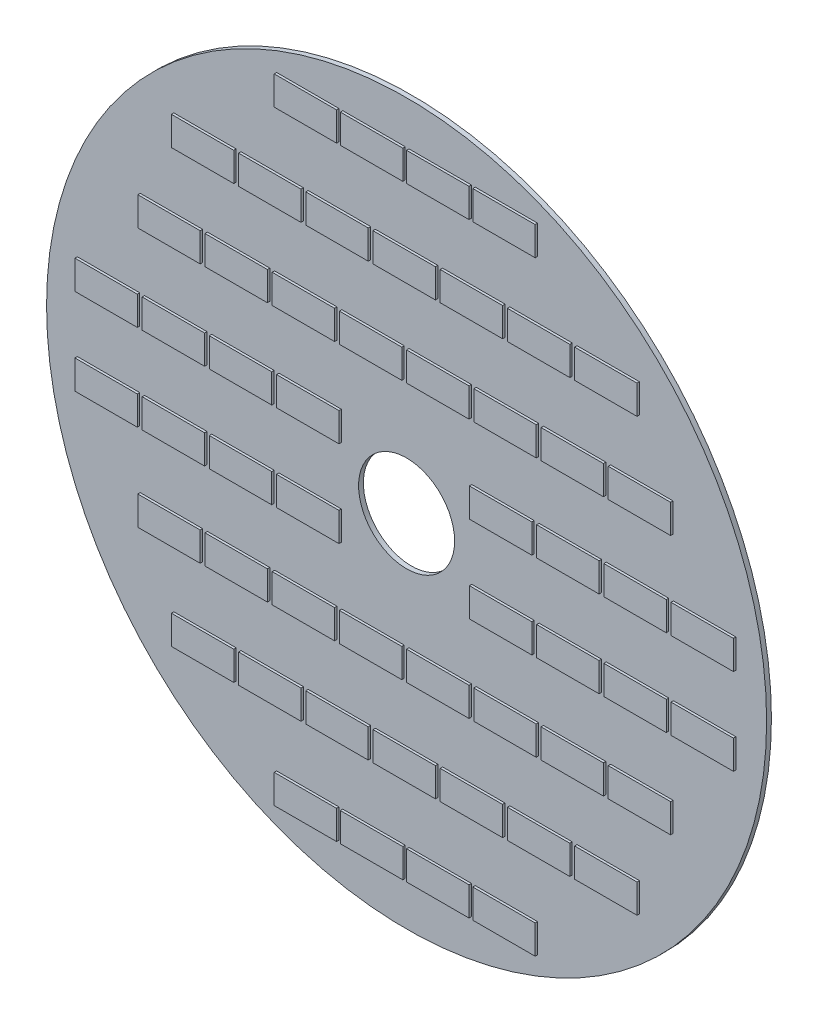
SolidWorks part; units mm, degrees
ref_plane "前视基准面" through (0, 0, 0) normal (0, 0, 1) x (1, 0, 0)
ref_plane "上视基准面" through (0, 0, 0) normal (0, 1, 0) x (1, 0, 0)
ref_plane "右视基准面" through (0, 0, 0) normal (1, 0, 0) x (0, 0, -1)
other "Configuration Table"
sketch "草图1" plane through (0, 0, 0) normal (0, 0, 1) x (1, 0, 0)
  line L5 (100, 90) -> (230, 90)
  line L6 (100, 90) -> (100, 30)
  line L8 (100, 30) -> (230, 30)
  line L12 (230, 90) -> (230, 30)
  line L14 (100, 90) -> (230, 30) construction
  line L18 (100, 30) -> (230, 90) construction
  line L24 (-1658.199, 0) -> (1658.199, 0) construction
  line L26 (0, 1113.9389) -> (0, -1113.9389) construction
  line L50 (300, 90) -> (430, 90)
  line L53 (300, 90) -> (300, 30)
  line L57 (300, 30) -> (430, 30)
  line L58 (430, 90) -> (430, 30)
  line L59 (300, 90) -> (430, 30) construction
  line L60 (300, 30) -> (430, 90) construction
  line L61 (37.3566, 180) -> (37.3566, 120)
  line L62 (237.3566, 120) -> (367.3566, 120)
  line L63 (237.3566, 180) -> (367.3566, 120) construction
  line L64 (37.3566, 120) -> (167.3566, 180) construction
  line L65 (237.3566, 180) -> (237.3566, 120)
  line L66 (367.3566, 180) -> (367.3566, 120)
  line L67 (37.3566, 180) -> (167.3566, 180)
  line L68 (37.3566, 180) -> (167.3566, 120) construction
  line L69 (237.3566, 180) -> (367.3566, 180)
  line L70 (237.3566, 120) -> (367.3566, 180) construction
  line L71 (37.3566, 120) -> (167.3566, 120)
  line L72 (167.3566, 180) -> (167.3566, 120)
  line L83 (37.3566, 364.2375) -> (37.3566, 304.2375)
  line L84 (237.3566, 304.2375) -> (367.3566, 304.2375)
  line L91 (133.7252, 270) -> (133.7252, 210)
  line L92 (333.7252, 210) -> (463.7252, 210)
  line L93 (333.7252, 270) -> (463.7252, 210) construction
  line L94 (133.7252, 210) -> (266.6142, 270) construction
  line L95 (333.7252, 270) -> (333.7252, 210)
  line L96 (463.7252, 270) -> (463.7252, 210)
  line L97 (133.7252, 270) -> (266.6142, 270)
  line L98 (133.7252, 270) -> (266.6142, 210) construction
  line L99 (333.7252, 270) -> (463.7252, 270)
  line L100 (333.7252, 210) -> (463.7252, 270) construction
  line L101 (133.7252, 210) -> (266.6142, 210)
  line L102 (266.6142, 270) -> (266.6142, 210)
  line L103 (-65, 274.2375) -> (-65, 210)
  line L104 (-65, 274.2375) -> (65, 274.2375)
  line L105 (-65, 210) -> (65, 210)
  line L106 (65, 274.2375) -> (65, 210)
  line L107 (-65, 210) -> (65, 274.2375) construction
  line L108 (-65, 274.2375) -> (65, 210) construction
  line L109 (-264.8303, 270) -> (-264.8303, 210)
  line L110 (-264.8303, 270) -> (-134.8303, 270)
  line L111 (-264.8303, 210) -> (-134.8303, 210)
  line L112 (-134.8303, 270) -> (-134.8303, 210)
  line L113 (-264.8303, 210) -> (-134.8303, 270) construction
  line L114 (-264.8303, 270) -> (-134.8303, 210) construction
  line L115 (-464.8303, 270) -> (-464.8303, 210)
  line L116 (-464.8303, 270) -> (-334.8303, 270)
  line L117 (-464.8303, 210) -> (-334.8303, 210)
  line L118 (-334.8303, 270) -> (-334.8303, 210)
  line L119 (-464.8303, 210) -> (-334.8303, 270) construction
  line L120 (-464.8303, 270) -> (-334.8303, 210) construction
  line L122 (237.3566, 364.2375) -> (237.3566, 304.2375)
  line L123 (367.3566, 364.2375) -> (367.3566, 304.2375)
  line L125 (37.3566, 364.2375) -> (167.3566, 364.2375)
  line L127 (237.3566, 364.2375) -> (367.3566, 364.2375)
  line L128 (37.3566, 304.2375) -> (167.3566, 304.2375)
  line L129 (167.3566, 364.2375) -> (167.3566, 304.2375)
  line L139 (237.3566, 364.2375) -> (367.3566, 304.2375) construction
  line L140 (37.3566, 304.2375) -> (167.3566, 364.2375) construction
  line L141 (37.3566, 364.2375) -> (167.3566, 304.2375) construction
  line L142 (237.3566, 304.2375) -> (367.3566, 364.2375) construction
  line L143 (37.3566, 450) -> (37.3566, 390)
  line L144 (237.3566, 390) -> (367.3566, 390)
  line L145 (237.3566, 450) -> (237.3566, 390)
  line L146 (367.3566, 450) -> (367.3566, 390)
  line L147 (37.3566, 450) -> (167.3566, 450)
  line L148 (237.3566, 450) -> (367.3566, 450)
  line L149 (37.3566, 390) -> (167.3566, 390)
  line L150 (167.3566, 450) -> (167.3566, 390)
  line L151 (237.3566, 450) -> (367.3566, 390) construction
  line L152 (37.3566, 390) -> (167.3566, 450) construction
  line L153 (37.3566, 450) -> (167.3566, 390) construction
  line L154 (237.3566, 390) -> (367.3566, 450) construction
  line L155 (37.3566, 535.7625) -> (37.3566, 475.7625)
  line L156 (237.3566, 475.7625) -> (367.3566, 475.7625)
  line L157 (237.3566, 535.7625) -> (237.3566, 475.7625)
  line L158 (367.3566, 535.7625) -> (367.3566, 475.7625)
  line L159 (37.3566, 535.7625) -> (167.3566, 535.7625)
  line L160 (237.3566, 535.7625) -> (367.3566, 535.7625)
  line L161 (37.3566, 475.7625) -> (167.3566, 475.7625)
  line L162 (167.3566, 535.7625) -> (167.3566, 475.7625)
  line L163 (237.3566, 535.7625) -> (367.3566, 475.7625) construction
  line L164 (37.3566, 475.7625) -> (167.3566, 535.7625) construction
  line L165 (37.3566, 535.7625) -> (167.3566, 475.7625) construction
  line L166 (237.3566, 475.7625) -> (367.3566, 535.7625) construction
  line L167 (-264.8303, 565.7625) -> (-134.8303, 625.7625) construction
  line L168 (133.7252, 565.7625) -> (266.6142, 565.7625)
  line L169 (-65, 565.7625) -> (65, 625.7625) construction
  line L170 (-65, 625.7625) -> (-65, 565.7625)
  line L171 (-264.8303, 625.7625) -> (-264.8303, 565.7625)
  line L172 (-134.8303, 625.7625) -> (-134.8303, 565.7625)
  line L173 (133.7252, 625.7625) -> (266.6142, 625.7625)
  line L174 (133.7252, 625.7625) -> (266.6142, 565.7625) construction
  line L175 (65, 625.7625) -> (65, 565.7625)
  line L176 (-264.8303, 625.7625) -> (-134.8303, 565.7625) construction
  line L177 (133.7252, 625.7625) -> (133.7252, 565.7625)
  line L178 (-65, 625.7625) -> (65, 625.7625)
  line L179 (-65, 565.7625) -> (65, 565.7625)
  line L180 (-264.8303, 565.7625) -> (-134.8303, 565.7625)
  line L181 (133.7252, 565.7625) -> (266.6142, 625.7625) construction
  line L182 (266.6142, 625.7625) -> (266.6142, 565.7625)
  line L183 (-264.8303, 625.7625) -> (-134.8303, 625.7625)
  line L184 (-65, 625.7625) -> (65, 565.7625) construction
  line L185 (-300, 90) -> (-300, 30)
  line L186 (-300, 30) -> (-430, 30)
  line L187 (-430, 90) -> (-430, 30)
  line L188 (-300, 90) -> (-430, 90)
  line L189 (-100, 30) -> (-230, 30)
  line L190 (-230, 90) -> (-230, 30)
  line L191 (-100, 90) -> (-230, 90)
  line L192 (-100, 90) -> (-100, 30)
  line L193 (-37.3566, 180) -> (-167.3566, 180)
  line L194 (-167.3566, 180) -> (-167.3566, 120)
  line L195 (-37.3566, 120) -> (-167.3566, 120)
  line L196 (-37.3566, 180) -> (-37.3566, 120)
  line L197 (-237.3566, 180) -> (-237.3566, 120)
  line L198 (-237.3566, 180) -> (-367.3566, 180)
  line L199 (-367.3566, 180) -> (-367.3566, 120)
  line L200 (-237.3566, 120) -> (-367.3566, 120)
  line L201 (-237.3566, 475.7625) -> (-367.3566, 535.7625) construction
  line L202 (-37.3566, 535.7625) -> (-167.3566, 475.7625) construction
  line L203 (-37.3566, 475.7625) -> (-167.3566, 535.7625) construction
  line L204 (-237.3566, 535.7625) -> (-367.3566, 475.7625) construction
  line L205 (-237.3566, 390) -> (-367.3566, 450) construction
  line L206 (-37.3566, 450) -> (-167.3566, 390) construction
  line L207 (-37.3566, 390) -> (-167.3566, 450) construction
  line L208 (-237.3566, 450) -> (-367.3566, 390) construction
  line L209 (-237.3566, 304.2375) -> (-367.3566, 364.2375) construction
  line L210 (-37.3566, 364.2375) -> (-167.3566, 304.2375) construction
  line L211 (-37.3566, 304.2375) -> (-167.3566, 364.2375) construction
  line L212 (-237.3566, 364.2375) -> (-367.3566, 304.2375) construction
  line L213 (-167.3566, 535.7625) -> (-167.3566, 475.7625)
  line L214 (-37.3566, 475.7625) -> (-167.3566, 475.7625)
  line L215 (-237.3566, 535.7625) -> (-367.3566, 535.7625)
  line L216 (-37.3566, 535.7625) -> (-167.3566, 535.7625)
  line L217 (-367.3566, 535.7625) -> (-367.3566, 475.7625)
  line L218 (-237.3566, 535.7625) -> (-237.3566, 475.7625)
  line L219 (-237.3566, 475.7625) -> (-367.3566, 475.7625)
  line L220 (-37.3566, 535.7625) -> (-37.3566, 475.7625)
  line L221 (-167.3566, 450) -> (-167.3566, 390)
  line L222 (-37.3566, 390) -> (-167.3566, 390)
  line L223 (-237.3566, 450) -> (-367.3566, 450)
  line L224 (-37.3566, 450) -> (-167.3566, 450)
  line L225 (-367.3566, 450) -> (-367.3566, 390)
  line L226 (-237.3566, 450) -> (-237.3566, 390)
  line L227 (-237.3566, 390) -> (-367.3566, 390)
  line L228 (-37.3566, 450) -> (-37.3566, 390)
  line L229 (-167.3566, 364.2375) -> (-167.3566, 304.2375)
  line L230 (-37.3566, 304.2375) -> (-167.3566, 304.2375)
  line L231 (-237.3566, 364.2375) -> (-367.3566, 364.2375)
  line L232 (-37.3566, 364.2375) -> (-167.3566, 364.2375)
  line L233 (-367.3566, 364.2375) -> (-367.3566, 304.2375)
  line L234 (-237.3566, 364.2375) -> (-237.3566, 304.2375)
  line L235 (-237.3566, 304.2375) -> (-367.3566, 304.2375)
  line L236 (-37.3566, 364.2375) -> (-37.3566, 304.2375)
  line L237 (-237.3566, -364.2375) -> (-367.3566, -304.2375) construction
  line L238 (-37.3566, -304.2375) -> (-167.3566, -364.2375) construction
  line L239 (-37.3566, -364.2375) -> (-167.3566, -304.2375) construction
  line L240 (-237.3566, -304.2375) -> (-367.3566, -364.2375) construction
  line L241 (-237.3566, -450) -> (-367.3566, -390) construction
  line L242 (-37.3566, -390) -> (-167.3566, -450) construction
  line L243 (-37.3566, -450) -> (-167.3566, -390) construction
  line L244 (-237.3566, -390) -> (-367.3566, -450) construction
  line L245 (-237.3566, -535.7625) -> (-367.3566, -475.7625) construction
  line L246 (-37.3566, -475.7625) -> (-167.3566, -535.7625) construction
  line L247 (-37.3566, -535.7625) -> (-167.3566, -475.7625) construction
  line L248 (-237.3566, -475.7625) -> (-367.3566, -535.7625) construction
  line L249 (-65, -625.7625) -> (65, -565.7625) construction
  line L250 (133.7252, -565.7625) -> (266.6142, -625.7625) construction
  line L251 (-264.8303, -625.7625) -> (-134.8303, -565.7625) construction
  line L252 (133.7252, -625.7625) -> (266.6142, -565.7625) construction
  line L253 (-65, -565.7625) -> (65, -625.7625) construction
  line L254 (-264.8303, -565.7625) -> (-134.8303, -625.7625) construction
  line L255 (237.3566, -475.7625) -> (367.3566, -535.7625) construction
  line L256 (37.3566, -535.7625) -> (167.3566, -475.7625) construction
  line L257 (37.3566, -475.7625) -> (167.3566, -535.7625) construction
  line L258 (237.3566, -535.7625) -> (367.3566, -475.7625) construction
  line L259 (237.3566, -390) -> (367.3566, -450) construction
  line L260 (37.3566, -450) -> (167.3566, -390) construction
  line L261 (37.3566, -390) -> (167.3566, -450) construction
  line L262 (237.3566, -450) -> (367.3566, -390) construction
  line L263 (237.3566, -304.2375) -> (367.3566, -364.2375) construction
  line L264 (37.3566, -364.2375) -> (167.3566, -304.2375) construction
  line L265 (37.3566, -304.2375) -> (167.3566, -364.2375) construction
  line L266 (237.3566, -364.2375) -> (367.3566, -304.2375) construction
  line L267 (-464.8303, -270) -> (-334.8303, -210) construction
  line L268 (-464.8303, -210) -> (-334.8303, -270) construction
  line L269 (-264.8303, -270) -> (-134.8303, -210) construction
  line L270 (-264.8303, -210) -> (-134.8303, -270) construction
  line L271 (-65, -274.2375) -> (65, -210) construction
  line L272 (-65, -210) -> (65, -274.2375) construction
  line L273 (333.7252, -210) -> (463.7252, -270) construction
  line L274 (133.7252, -270) -> (266.6142, -210) construction
  line L275 (133.7252, -210) -> (266.6142, -270) construction
  line L276 (333.7252, -270) -> (463.7252, -210) construction
  line L277 (237.3566, -120) -> (367.3566, -180) construction
  line L278 (37.3566, -180) -> (167.3566, -120) construction
  line L279 (37.3566, -120) -> (167.3566, -180) construction
  line L280 (237.3566, -180) -> (367.3566, -120) construction
  line L281 (300, -30) -> (430, -90) construction
  line L282 (300, -90) -> (430, -30) construction
  line L283 (100, -30) -> (230, -90) construction
  line L284 (100, -90) -> (230, -30) construction
  line L285 (-37.3566, -364.2375) -> (-37.3566, -304.2375)
  line L286 (-237.3566, -304.2375) -> (-367.3566, -304.2375)
  line L287 (-237.3566, -364.2375) -> (-237.3566, -304.2375)
  line L288 (-367.3566, -364.2375) -> (-367.3566, -304.2375)
  line L289 (-37.3566, -364.2375) -> (-167.3566, -364.2375)
  line L290 (-237.3566, -364.2375) -> (-367.3566, -364.2375)
  line L291 (-37.3566, -304.2375) -> (-167.3566, -304.2375)
  line L292 (-167.3566, -364.2375) -> (-167.3566, -304.2375)
  line L293 (-37.3566, -450) -> (-37.3566, -390)
  line L294 (-237.3566, -390) -> (-367.3566, -390)
  line L295 (-237.3566, -450) -> (-237.3566, -390)
  line L296 (-367.3566, -450) -> (-367.3566, -390)
  line L297 (-37.3566, -450) -> (-167.3566, -450)
  line L298 (-237.3566, -450) -> (-367.3566, -450)
  line L299 (-37.3566, -390) -> (-167.3566, -390)
  line L300 (-167.3566, -450) -> (-167.3566, -390)
  line L301 (-37.3566, -535.7625) -> (-37.3566, -475.7625)
  line L302 (-237.3566, -475.7625) -> (-367.3566, -475.7625)
  line L303 (-237.3566, -535.7625) -> (-237.3566, -475.7625)
  line L304 (-367.3566, -535.7625) -> (-367.3566, -475.7625)
  line L305 (-37.3566, -535.7625) -> (-167.3566, -535.7625)
  line L306 (-237.3566, -535.7625) -> (-367.3566, -535.7625)
  line L307 (-37.3566, -475.7625) -> (-167.3566, -475.7625)
  line L308 (-167.3566, -535.7625) -> (-167.3566, -475.7625)
  line L309 (-237.3566, -120) -> (-367.3566, -120)
  line L310 (-367.3566, -180) -> (-367.3566, -120)
  line L311 (-237.3566, -180) -> (-367.3566, -180)
  line L312 (-237.3566, -180) -> (-237.3566, -120)
  line L313 (-37.3566, -180) -> (-37.3566, -120)
  line L314 (-37.3566, -120) -> (-167.3566, -120)
  line L315 (-167.3566, -180) -> (-167.3566, -120)
  line L316 (-37.3566, -180) -> (-167.3566, -180)
  line L317 (-100, -90) -> (-100, -30)
  line L318 (-100, -90) -> (-230, -90)
  line L319 (-230, -90) -> (-230, -30)
  line L320 (-100, -30) -> (-230, -30)
  line L321 (-300, -90) -> (-430, -90)
  line L322 (-430, -90) -> (-430, -30)
  line L323 (-300, -30) -> (-430, -30)
  line L324 (-300, -90) -> (-300, -30)
  line L325 (-264.8303, -625.7625) -> (-134.8303, -625.7625)
  line L326 (266.6142, -625.7625) -> (266.6142, -565.7625)
  line L327 (-264.8303, -565.7625) -> (-134.8303, -565.7625)
  line L328 (-65, -565.7625) -> (65, -565.7625)
  line L329 (-65, -625.7625) -> (65, -625.7625)
  line L330 (133.7252, -625.7625) -> (133.7252, -565.7625)
  line L331 (65, -625.7625) -> (65, -565.7625)
  line L332 (133.7252, -625.7625) -> (266.6142, -625.7625)
  line L333 (-134.8303, -625.7625) -> (-134.8303, -565.7625)
  line L334 (-264.8303, -625.7625) -> (-264.8303, -565.7625)
  line L335 (-65, -625.7625) -> (-65, -565.7625)
  line L336 (133.7252, -565.7625) -> (266.6142, -565.7625)
  line L337 (167.3566, -535.7625) -> (167.3566, -475.7625)
  line L338 (37.3566, -475.7625) -> (167.3566, -475.7625)
  line L339 (237.3566, -535.7625) -> (367.3566, -535.7625)
  line L340 (37.3566, -535.7625) -> (167.3566, -535.7625)
  line L341 (367.3566, -535.7625) -> (367.3566, -475.7625)
  line L342 (237.3566, -535.7625) -> (237.3566, -475.7625)
  line L343 (237.3566, -475.7625) -> (367.3566, -475.7625)
  line L344 (37.3566, -535.7625) -> (37.3566, -475.7625)
  line L345 (167.3566, -450) -> (167.3566, -390)
  line L346 (37.3566, -390) -> (167.3566, -390)
  line L347 (237.3566, -450) -> (367.3566, -450)
  line L348 (37.3566, -450) -> (167.3566, -450)
  line L349 (367.3566, -450) -> (367.3566, -390)
  line L350 (237.3566, -450) -> (237.3566, -390)
  line L351 (237.3566, -390) -> (367.3566, -390)
  line L352 (37.3566, -450) -> (37.3566, -390)
  line L353 (167.3566, -364.2375) -> (167.3566, -304.2375)
  line L354 (37.3566, -304.2375) -> (167.3566, -304.2375)
  line L355 (237.3566, -364.2375) -> (367.3566, -364.2375)
  line L356 (37.3566, -364.2375) -> (167.3566, -364.2375)
  line L357 (367.3566, -364.2375) -> (367.3566, -304.2375)
  line L358 (237.3566, -364.2375) -> (237.3566, -304.2375)
  line L359 (-334.8303, -270) -> (-334.8303, -210)
  line L360 (-464.8303, -210) -> (-334.8303, -210)
  line L361 (-464.8303, -270) -> (-334.8303, -270)
  line L362 (-464.8303, -270) -> (-464.8303, -210)
  line L363 (-134.8303, -270) -> (-134.8303, -210)
  line L364 (-264.8303, -210) -> (-134.8303, -210)
  line L365 (-264.8303, -270) -> (-134.8303, -270)
  line L366 (-264.8303, -270) -> (-264.8303, -210)
  line L367 (65, -274.2375) -> (65, -210)
  line L368 (-65, -210) -> (65, -210)
  line L369 (-65, -274.2375) -> (65, -274.2375)
  line L370 (-65, -274.2375) -> (-65, -210)
  line L371 (266.6142, -270) -> (266.6142, -210)
  line L372 (133.7252, -210) -> (266.6142, -210)
  line L373 (333.7252, -270) -> (463.7252, -270)
  line L374 (133.7252, -270) -> (266.6142, -270)
  line L375 (463.7252, -270) -> (463.7252, -210)
  line L376 (333.7252, -270) -> (333.7252, -210)
  line L377 (333.7252, -210) -> (463.7252, -210)
  line L378 (133.7252, -270) -> (133.7252, -210)
  line L379 (237.3566, -304.2375) -> (367.3566, -304.2375)
  line L380 (37.3566, -364.2375) -> (37.3566, -304.2375)
  line L381 (167.3566, -180) -> (167.3566, -120)
  line L382 (37.3566, -120) -> (167.3566, -120)
  line L383 (237.3566, -180) -> (367.3566, -180)
  line L384 (37.3566, -180) -> (167.3566, -180)
  line L385 (367.3566, -180) -> (367.3566, -120)
  line L386 (237.3566, -180) -> (237.3566, -120)
  line L387 (237.3566, -120) -> (367.3566, -120)
  line L388 (37.3566, -180) -> (37.3566, -120)
  line L389 (430, -90) -> (430, -30)
  line L390 (300, -30) -> (430, -30)
  line L391 (300, -90) -> (300, -30)
  line L392 (300, -90) -> (430, -90)
  line L393 (230, -90) -> (230, -30)
  line L394 (100, -30) -> (230, -30)
  line L395 (100, -90) -> (100, -30)
  line L396 (100, -90) -> (230, -90)
  line L397 (-65, 715.7625) -> (65, 715.7625)
  line L398 (-65, 715.7625) -> (65, 655.7625) construction
  line L399 (65, 715.7625) -> (65, 655.7625)
  line L400 (-65, 655.7625) -> (65, 715.7625) construction
  line L401 (-65, 715.7625) -> (-65, 655.7625)
  line L402 (-65, 655.7625) -> (65, 655.7625)
  line L403 (-65, -655.7625) -> (65, -715.7625) construction
  line L404 (-65, -715.7625) -> (65, -655.7625) construction
  line L405 (-65, -655.7625) -> (65, -655.7625)
  line L406 (-65, -715.7625) -> (-65, -655.7625)
  line L407 (65, -715.7625) -> (65, -655.7625)
  line L408 (-65, -715.7625) -> (65, -715.7625)
  circle A0 centre (0, 0) radius 750 construction
  point P0 (165, 60)
  point P5 (102.3566, 150)
  point P7 (365, 60)
  point P16 (302.3566, 192.8005)
  point P24 (200.1697, 595.7625)
  point P26 (200.1697, 240)
  point P29 (102.3566, 334.2375)
  point P39 (102.3566, 420)
  point P47 (0, 274.2375)
  point P70 (102.3566, 505.7625)
  point P80 (302.3566, 462.8005)
  point P81 (302.3566, 377.038)
  point P132 (-102.3566, 505.7625)
  point P133 (-102.3566, 420)
  point P134 (-102.3566, 334.2375)
  point P247 (-102.3566, -334.2375)
  point P248 (-102.3566, -420)
  point P249 (-102.3566, -505.7625)
  point P250 (102.3566, -505.7625)
  point P251 (102.3566, -420)
  point P252 (102.3566, -334.2375)
  point P253 (200.1697, -240)
  point P254 (200.1697, -595.7625)
  point P255 (302.3566, -192.8005)
  point P256 (365, -60)
  point P257 (102.3566, -150)
  point P258 (165, -60)
  dimension "D3" = 100
  dimension "D1" = 2
  dimension "D2" = 30
  dimension "D4" = 30
  dimension "D5" = 60
  dimension "D6" = 130
  dimension "D7" = 70
  dimension "D8" = 70
  dimension "D9" = 2
  dimension "D10" = 3
  dimension "D11" = 130
  dimension "D12" = 60
  dimension "D13" = 30
  dimension "D14" = 60
  dimension "D15" = 30
sketch "草图2" plane through (0, 0, 0) normal (0, 0, 1) x (1, 0, 0)
  circle A0 centre (0, 0) radius 750
  circle A1 centre (0, 0) radius 100
  dimension "D1" = 1500
  dimension "D2" = 200
extrude "凸台-拉伸1" add sketch "草图2" along normal blind 10
sketch "草图3" plane through (0, 0, 0) normal (0, 0, 1) x (1, 0, 0)
  line L0 (-1673.2224, 0) -> (1673.2224, 0) construction
  line L2 (135.9057, 120) -> (265.9057, 120)
  line L3 (0, -869.8968) -> (0, 1064.1184) construction
  line L4 (135.9057, 120) -> (135.9057, 60)
  line L5 (135.9057, 60) -> (265.9057, 60)
  line L6 (265.9057, 120) -> (265.9057, 60)
  line L18 (275.9057, 120) -> (275.9057, 60)
  line L19 (275.9057, 120) -> (405.9057, 120)
  line L20 (405.9057, 120) -> (405.9057, 60)
  line L21 (275.9057, 60) -> (405.9057, 60)
  line L22 (415.9057, 120) -> (415.9057, 60)
  line L23 (415.9057, 120) -> (545.9057, 120)
  line L24 (545.9057, 120) -> (545.9057, 60)
  line L25 (415.9057, 60) -> (545.9057, 60)
  line L26 (555.9057, 120) -> (555.9057, 60)
  line L27 (555.9057, 120) -> (685.9057, 120)
  line L28 (685.9057, 120) -> (685.9057, 60)
  line L29 (555.9057, 60) -> (685.9057, 60)
  line L30 (145, 300) -> (145, 240)
  line L31 (-555.9057, 60) -> (-685.9057, 60)
  line L32 (-685.9057, 120) -> (-685.9057, 60)
  line L33 (-555.9057, 120) -> (-685.9057, 120)
  line L34 (-555.9057, 120) -> (-555.9057, 60)
  line L35 (-415.9057, 60) -> (-545.9057, 60)
  line L36 (-545.9057, 120) -> (-545.9057, 60)
  line L37 (-415.9057, 120) -> (-545.9057, 120)
  line L38 (-415.9057, 120) -> (-415.9057, 60)
  line L39 (-275.9057, 60) -> (-405.9057, 60)
  line L40 (-405.9057, 120) -> (-405.9057, 60)
  line L41 (-275.9057, 120) -> (-405.9057, 120)
  line L42 (-275.9057, 120) -> (-275.9057, 60)
  line L43 (-265.9057, 120) -> (-265.9057, 60)
  line L44 (-135.9057, 60) -> (-265.9057, 60)
  line L45 (-135.9057, 120) -> (-135.9057, 60)
  line L46 (-135.9057, 120) -> (-265.9057, 120)
  line L47 (145, 300) -> (275, 300)
  line L48 (5, 300) -> (135, 300)
  line L49 (5, 300) -> (5, 240)
  line L50 (5, 240) -> (135, 240)
  line L51 (135, 300) -> (135, 240)
  line L52 (275, 300) -> (275, 240)
  line L53 (145, 240) -> (275, 240)
  line L54 (285, 300) -> (285, 240)
  line L55 (285, 300) -> (415, 300)
  line L56 (415, 300) -> (415, 240)
  line L57 (285, 240) -> (415, 240)
  line L58 (425, 300) -> (425, 240)
  line L59 (425, 300) -> (555, 300)
  line L60 (555, 300) -> (555, 240)
  line L61 (425, 240) -> (555, 240)
  line L62 (-425, 240) -> (-555, 240)
  line L63 (-555, 300) -> (-555, 240)
  line L64 (-425, 300) -> (-555, 300)
  line L65 (-425, 300) -> (-425, 240)
  line L66 (-285, 240) -> (-415, 240)
  line L67 (-415, 300) -> (-415, 240)
  line L68 (-285, 300) -> (-415, 300)
  line L69 (-285, 300) -> (-285, 240)
  line L70 (-145, 240) -> (-275, 240)
  line L71 (-275, 300) -> (-275, 240)
  line L72 (-135, 300) -> (-135, 240)
  line L73 (-5, 240) -> (-135, 240)
  line L74 (-5, 300) -> (-5, 240)
  line L75 (-5, 300) -> (-135, 300)
  line L76 (-145, 300) -> (-275, 300)
  line L77 (-145, 300) -> (-145, 240)
  line L78 (75, 480) -> (205, 480)
  line L79 (-65, 480) -> (65, 480)
  line L80 (-65, 480) -> (-65, 420)
  line L81 (-65, 420) -> (65, 420)
  line L82 (65, 480) -> (65, 420)
  line L83 (75, 480) -> (75, 420)
  line L84 (75, 420) -> (205, 420)
  line L85 (205, 480) -> (205, 420)
  line L86 (215, 480) -> (345, 480)
  line L87 (215, 480) -> (215, 420)
  line L88 (215, 420) -> (345, 420)
  line L89 (345, 480) -> (345, 420)
  line L90 (355, 480) -> (485, 480)
  line L91 (355, 480) -> (355, 420)
  line L92 (355, 420) -> (485, 420)
  line L93 (485, 480) -> (485, 420)
  line L94 (-485, 480) -> (-485, 420)
  line L95 (-355, 420) -> (-485, 420)
  line L96 (-355, 480) -> (-355, 420)
  line L97 (-355, 480) -> (-485, 480)
  line L98 (-345, 480) -> (-345, 420)
  line L99 (-215, 420) -> (-345, 420)
  line L100 (-215, 480) -> (-215, 420)
  line L101 (-215, 480) -> (-345, 480)
  line L102 (-205, 480) -> (-205, 420)
  line L103 (-75, 420) -> (-205, 420)
  line L104 (-75, 480) -> (-75, 420)
  line L105 (-75, 480) -> (-205, 480)
  line L106 (-132.9073, 660) -> (-132.9073, 600)
  line L107 (-270.8146, 660) -> (-140.8146, 660)
  line L108 (-270.8146, 660) -> (-270.8146, 600)
  line L109 (-270.8146, 600) -> (-140.8146, 600)
  line L110 (-140.8146, 660) -> (-140.8146, 600)
  line L111 (-132.9073, 660) -> (-2.9073, 660)
  line L112 (-2.9073, 660) -> (-2.9073, 600)
  line L113 (-132.9073, 600) -> (-2.9073, 600)
  line L114 (5, 660) -> (5, 600)
  line L115 (5, 660) -> (135, 660)
  line L116 (135, 660) -> (135, 600)
  line L117 (5, 600) -> (135, 600)
  line L118 (142.9073, 660) -> (142.9073, 600)
  line L119 (142.9073, 660) -> (272.9073, 660)
  line L120 (272.9073, 660) -> (272.9073, 600)
  line L121 (142.9073, 600) -> (272.9073, 600)
  line L122 (142.9073, -600) -> (272.9073, -600)
  line L123 (272.9073, -660) -> (272.9073, -600)
  line L124 (142.9073, -660) -> (272.9073, -660)
  line L125 (142.9073, -660) -> (142.9073, -600)
  line L126 (5, -600) -> (135, -600)
  line L127 (135, -660) -> (135, -600)
  line L128 (5, -660) -> (135, -660)
  line L129 (5, -660) -> (5, -600)
  line L130 (-132.9073, -600) -> (-2.9073, -600)
  line L131 (-2.9073, -660) -> (-2.9073, -600)
  line L132 (-132.9073, -660) -> (-2.9073, -660)
  line L133 (-140.8146, -660) -> (-140.8146, -600)
  line L134 (-270.8146, -600) -> (-140.8146, -600)
  line L135 (-270.8146, -660) -> (-270.8146, -600)
  line L136 (-270.8146, -660) -> (-140.8146, -660)
  line L137 (-132.9073, -660) -> (-132.9073, -600)
  line L138 (-75, -480) -> (-205, -480)
  line L139 (-75, -480) -> (-75, -420)
  line L140 (-75, -420) -> (-205, -420)
  line L141 (-205, -480) -> (-205, -420)
  line L142 (-215, -480) -> (-345, -480)
  line L143 (-215, -480) -> (-215, -420)
  line L144 (-215, -420) -> (-345, -420)
  line L145 (-345, -480) -> (-345, -420)
  line L146 (-355, -480) -> (-485, -480)
  line L147 (-355, -480) -> (-355, -420)
  line L148 (-355, -420) -> (-485, -420)
  line L149 (-485, -480) -> (-485, -420)
  line L150 (485, -480) -> (485, -420)
  line L151 (355, -420) -> (485, -420)
  line L152 (355, -480) -> (355, -420)
  line L153 (355, -480) -> (485, -480)
  line L154 (345, -480) -> (345, -420)
  line L155 (215, -420) -> (345, -420)
  line L156 (215, -480) -> (215, -420)
  line L157 (215, -480) -> (345, -480)
  line L158 (205, -480) -> (205, -420)
  line L159 (75, -420) -> (205, -420)
  line L160 (75, -480) -> (75, -420)
  line L161 (65, -480) -> (65, -420)
  line L162 (-65, -420) -> (65, -420)
  line L163 (-65, -480) -> (-65, -420)
  line L164 (-65, -480) -> (65, -480)
  line L165 (75, -480) -> (205, -480)
  line L166 (-145, -300) -> (-145, -240)
  line L167 (-145, -300) -> (-275, -300)
  line L168 (-5, -300) -> (-135, -300)
  line L169 (-5, -300) -> (-5, -240)
  line L170 (-5, -240) -> (-135, -240)
  line L171 (-135, -300) -> (-135, -240)
  line L172 (-275, -300) -> (-275, -240)
  line L173 (-145, -240) -> (-275, -240)
  line L174 (-285, -300) -> (-285, -240)
  line L175 (-285, -300) -> (-415, -300)
  line L176 (-415, -300) -> (-415, -240)
  line L177 (-285, -240) -> (-415, -240)
  line L178 (-425, -300) -> (-425, -240)
  line L179 (-425, -300) -> (-555, -300)
  line L180 (-555, -300) -> (-555, -240)
  line L181 (-425, -240) -> (-555, -240)
  line L182 (425, -240) -> (555, -240)
  line L183 (555, -300) -> (555, -240)
  line L184 (425, -300) -> (555, -300)
  line L185 (425, -300) -> (425, -240)
  line L186 (285, -240) -> (415, -240)
  line L187 (415, -300) -> (415, -240)
  line L188 (285, -300) -> (415, -300)
  line L189 (285, -300) -> (285, -240)
  line L190 (145, -240) -> (275, -240)
  line L191 (275, -300) -> (275, -240)
  line L192 (135, -300) -> (135, -240)
  line L193 (5, -240) -> (135, -240)
  line L194 (5, -300) -> (5, -240)
  line L195 (5, -300) -> (135, -300)
  line L196 (145, -300) -> (275, -300)
  line L197 (-135.9057, -120) -> (-265.9057, -120)
  line L198 (-135.9057, -120) -> (-135.9057, -60)
  line L199 (-135.9057, -60) -> (-265.9057, -60)
  line L200 (-265.9057, -120) -> (-265.9057, -60)
  line L201 (-275.9057, -120) -> (-275.9057, -60)
  line L202 (-275.9057, -120) -> (-405.9057, -120)
  line L203 (-405.9057, -120) -> (-405.9057, -60)
  line L204 (-275.9057, -60) -> (-405.9057, -60)
  line L205 (-415.9057, -120) -> (-415.9057, -60)
  line L206 (-415.9057, -120) -> (-545.9057, -120)
  line L207 (-545.9057, -120) -> (-545.9057, -60)
  line L208 (-415.9057, -60) -> (-545.9057, -60)
  line L209 (-555.9057, -120) -> (-555.9057, -60)
  line L210 (-555.9057, -120) -> (-685.9057, -120)
  line L211 (-685.9057, -120) -> (-685.9057, -60)
  line L212 (-555.9057, -60) -> (-685.9057, -60)
  line L213 (145, -300) -> (145, -240)
  line L214 (555.9057, -60) -> (685.9057, -60)
  line L215 (685.9057, -120) -> (685.9057, -60)
  line L216 (555.9057, -120) -> (685.9057, -120)
  line L217 (555.9057, -120) -> (555.9057, -60)
  line L218 (415.9057, -60) -> (545.9057, -60)
  line L219 (545.9057, -120) -> (545.9057, -60)
  line L220 (415.9057, -120) -> (545.9057, -120)
  line L221 (415.9057, -120) -> (415.9057, -60)
  line L222 (275.9057, -60) -> (405.9057, -60)
  line L223 (405.9057, -120) -> (405.9057, -60)
  line L224 (275.9057, -120) -> (405.9057, -120)
  line L225 (275.9057, -120) -> (275.9057, -60)
  line L226 (265.9057, -120) -> (265.9057, -60)
  line L227 (135.9057, -60) -> (265.9057, -60)
  line L228 (135.9057, -120) -> (135.9057, -60)
  line L229 (135.9057, -120) -> (265.9057, -120)
  point P4 (0, 0)
  point P6 (0, 0)
  point P75 (0, 480)
  dimension "D1" = 130
  dimension "D2" = 60
  dimension "D5" = 130
  dimension "D4" = 60
  dimension "D6" = 60
  dimension "D8" = 5
  dimension "D9" = 120
  dimension "D10" = 130
  dimension "D11" = 60
  dimension "D13" = 130
  dimension "D14" = 60
  dimension "D16" = 5
  dimension "D17" = 120
  dimension "D18" = 120
  dimension "D3" = 4
  dimension "D7" = 4
  dimension "D12" = 4
  dimension "D15" = 4
extrude "凸台-拉伸2" add sketch "草图3" along normal blind 15
